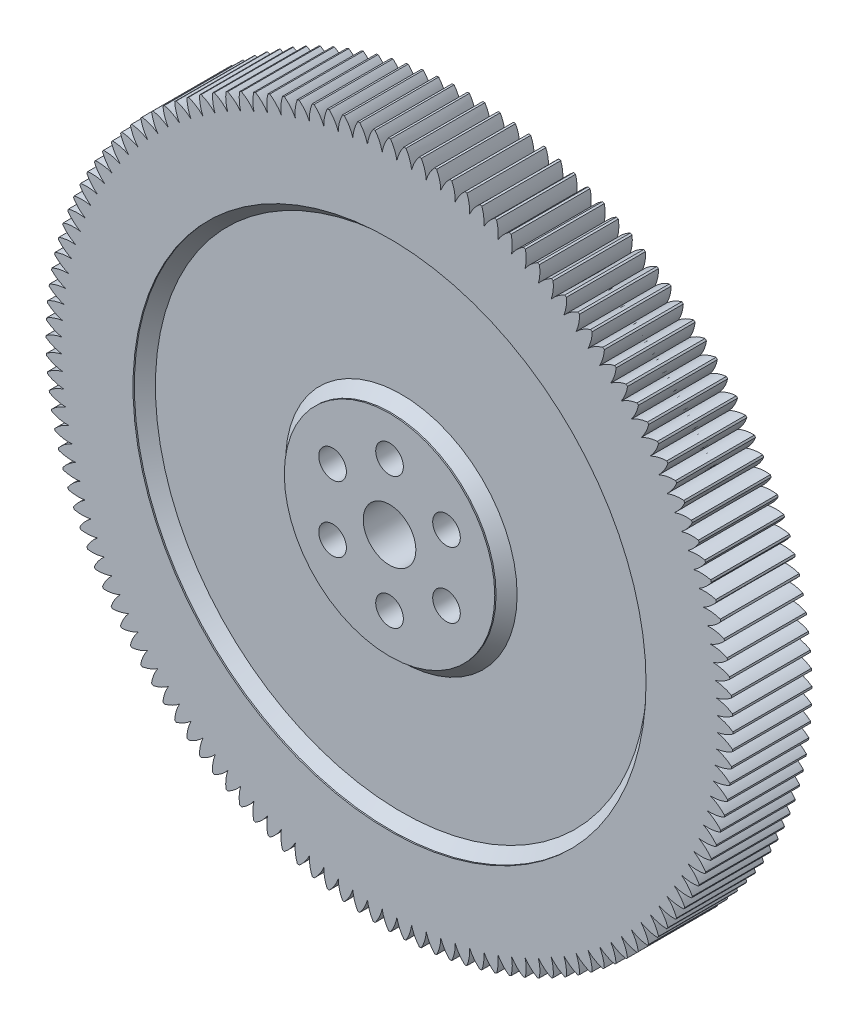
SolidWorks part; units mm, degrees
material "Cast iron, gray, flake graphite, EN GJL 250"
ref_plane "Front Plane" through (0, 0, 0) normal (0, 0, 1) x (1, 0, 0)
ref_plane "Top Plane" through (0, 0, 0) normal (0, 1, 0) x (1, 0, 0)
ref_plane "Right Plane" through (0, 0, 0) normal (1, 0, 0) x (0, 0, -1)
sketch "Sketch8" plane through (0, 0, 0) normal (0, 0, 1) x (1, 0, 0)
  circle A0 centre (0, 0) radius 97.5
  circle A1 centre (0, 0) radius 122.5
  dimension "D1" = 245
  dimension "D2" = 195
extrude "Boss-Extrude1" add sketch "Sketch8" along normal mid plane 30
sketch "Sketch9" plane through (0, 0, 0) normal (0, 0, 1) x (1, 0, 0)
  circle A0 centre (0, 0) radius 40
  dimension "D1" = 80
extrude "Boss-Extrude2" add sketch "Sketch9" along normal mid plane 30 separate body
sketch "Sketch10" plane through (0, 0, 0) normal (0, 0, 1) x (1, 0, 0)
  circle A0 centre (0, 0) radius 40
  circle A1 centre (0, 0) radius 97.5
  circle A2 centre (0, 0) radius 40 construction
  circle A3 centre (0, 0) radius 97.5 construction
extrude "Boss-Extrude3" add sketch "Sketch10" along normal mid plane 21
chamfer "Chamfer2" distance 4 angle 45 4 edges at (97.5, 0, 10.5) (40, 0, 10.5) (97.5, 0, -10.5) (40, 0, -10.5)
sketch "Sketch11" plane through (0, 0, 15) normal (0, 0, 1) x (1, 0, 0)
  circle A0 centre (0, 0) radius 10
  dimension "D1" = 20
extrude "Cut-Extrude1" cut sketch "Sketch11" against normal through all
ref_axis "Axis1" through (0, 0, -2.82) along (0, 0, 1)
sketch "Sketch13" plane through (0, 0, 15) normal (0, 0, 1) x (1, 0, 0)
  line L0 (-0.375, 130.5) -> (0.375, 130.5)
  line L1 (4.7384, 137.8027) -> (-5.4884, 123.1973) construction
  line L2 (0, 130.5) -> (0, 122.5) construction
  circle A0 centre (0, 0) radius 122.5 construction
  arc A1 (3, 122.4633) -> (-3, 122.4633) centre (0, 0) ccw
  spline S0 degree 2 poles (-3, 122.4633) (-2.8086, 127.0245) (-0.375, 130.5) knots 0 0 0 0.951846 0.951846 0.951846
  spline S1 degree 2 poles (3, 122.4633) (2.8086, 127.0245) (0.375, 130.5) knots 0 0 0 0.951846 0.951846 0.951846
  dimension "D1" = 55
  dimension "D3" = 8
  dimension "D4" = 6
  dimension "D5" = 8.4857
  dimension "D2" = 0.75
extrude "Boss-Extrude4" add sketch "Sketch13" against normal up to surface (30 mm away) up to face at (122.5, 0, -15)
pattern_circular "CirPattern2" count 140 over 360 about axis through (0, 0, 15) along (0, 0, -1) of "Boss-Extrude4"
hole_wizard "M12x1.5 Tapped Hole1" positions "Sketch14" profile "Sketch15" tap size "M12x1.5" standard "ANSI Metric" end condition through all
sketch "Sketch14" plane through (0, 0, 15) normal (0, 0, 1) x (1, 0, 0)
  line L1 (0, 10) -> (0, 40) construction
  circle A4 centre (0, 0) radius 40 construction
  circle A5 centre (0, 0) radius 10 construction
  point P127 (0, 25)
cosmetic thread "Hole Thread1" parameters "D2"=12
sketch "Sketch15" plane through (0, 25, 15) normal (1, 0, 0) x (0, -1, 0)
  line L0 (0, 0) -> (0, 30)
  line L1 (0, 30) -> (5.25, 30)
  line L2 (5.25, 30) -> (5.25, 0)
  line L5 (5.25, 0) -> (0, 0)
  line L11 (0, -6.35) -> (0, 107.95) construction
  dimension "Thru Tap Drill Dia." = 10.5
  dimension "Thru Tap Drill Depth" = 30
pattern_circular "CirPattern3" count 6 over 360 about axis through (0, 0, -2.82) along (0, 0, 1) of "M12x1.5 Tapped Hole1"
cosmetic thread "Hole Thread2" parameters "D2"=12
cosmetic thread "Hole Thread3" parameters "D2"=12
cosmetic thread "Hole Thread4" parameters "D2"=12
cosmetic thread "Hole Thread5" parameters "D2"=12
cosmetic thread "Hole Thread6" parameters "D2"=12
equation "\"Flywheel Diameter\"= 245mm"
equation "\"Crankshaft Radius\"= 20mm"
equation "\"Flywheel Thickness\"= 30mm"
equation "\"D1@Sketch8\"=\"Flywheel Diameter\""
equation "\"D2@Sketch8\"=\"Flywheel Diameter\"-50mm"
equation "\"D1@Boss-Extrude1\"=\"Flywheel Thickness\""
equation "\"Hub Diameter\"= \"Crankshaft Radius\" + 60mm"
equation "\"D1@Sketch9\"=\"Hub Diameter\""
equation "\"D1@Boss-Extrude2\"=\"Flywheel Thickness\""
equation "\"D1@Boss-Extrude3\"=\"Flywheel Thickness\"*0.7"
equation "\"D1@Sketch11\"=\"Crankshaft Radius\""
